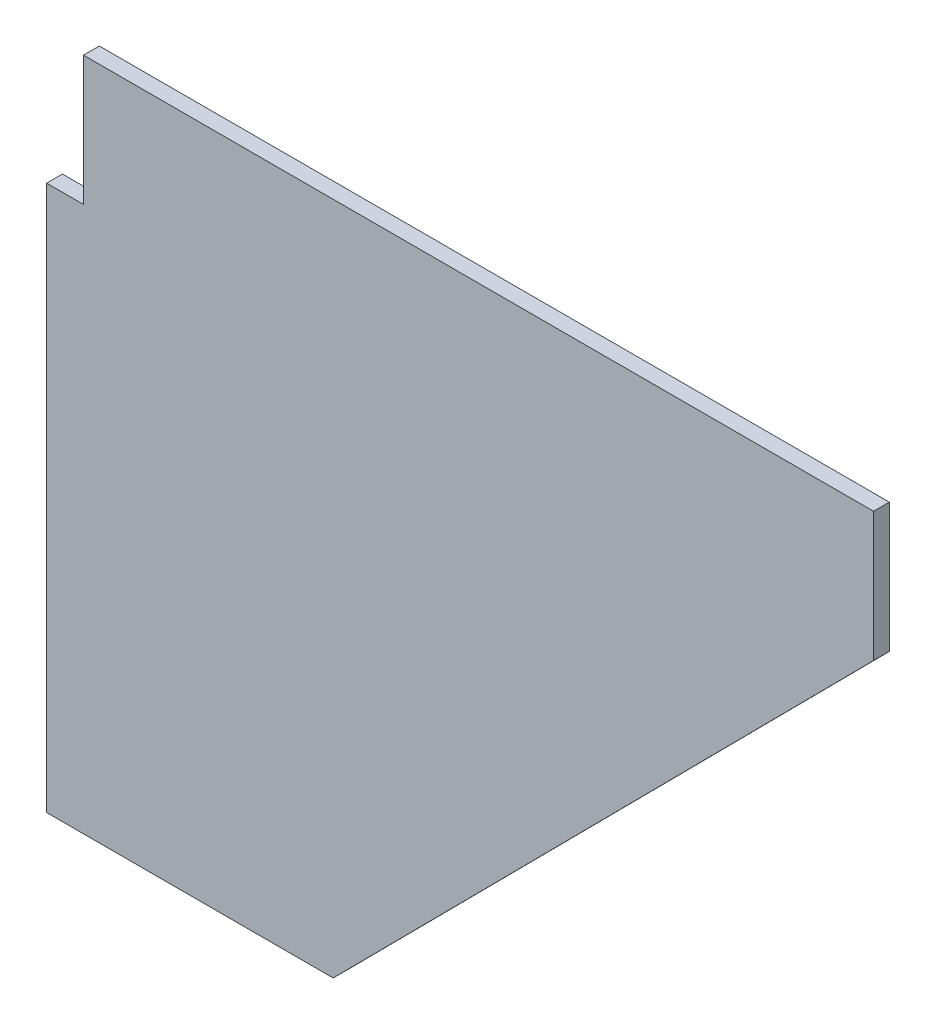
SolidWorks part; units mm, degrees
material "Zoltek Panex 33"
ref_plane "Plan de face" through (0, 0, 0) normal (0, 0, 1) x (1, 0, 0)
ref_plane "Plan de dessus" through (0, 0, 0) normal (0, 1, 0) x (1, 0, 0)
ref_plane "Plan de droite" through (0, 0, 0) normal (1, 0, 0) x (0, 0, -1)
sketch "Esquisse2" plane through (0, 0, 0) normal (0, 0, 1) x (1, 0, 0)
  line L0 (6.2308, -24.551) -> (13.2308, -24.551)
  line L1 (13.2308, -24.551) -> (13.2308, 0)
  line L2 (13.2308, 0) -> (163.2308, 0)
  line L3 (163.2308, 0) -> (163.2308, -24.551)
  line L4 (163.2308, -24.551) -> (60.6362, -128.0384)
  line L5 (60.6362, -128.0384) -> (6.2308, -128.0384)
  line L6 (6.2308, -128.0384) -> (6.2308, -24.551)
  line L7 (13.2308, 0) -> (0, 0) construction
  line L8 (6.2308, -24.551) -> (6.2308, 127.849) construction
  line L9 (6.2308, -24.551) -> (13.2308, -24.551) construction
  line L10 (13.2308, 88.4426) -> (13.2308, -24.5362) construction
  line L11 (163.2308, -24.5362) -> (163.2308, -21.9449) construction
  line L12 (163.2308, -24.551) -> (1232.4308, -24.551) construction
extrude "Boss.-Extru.1" add sketch "Esquisse2" along normal blind 3
